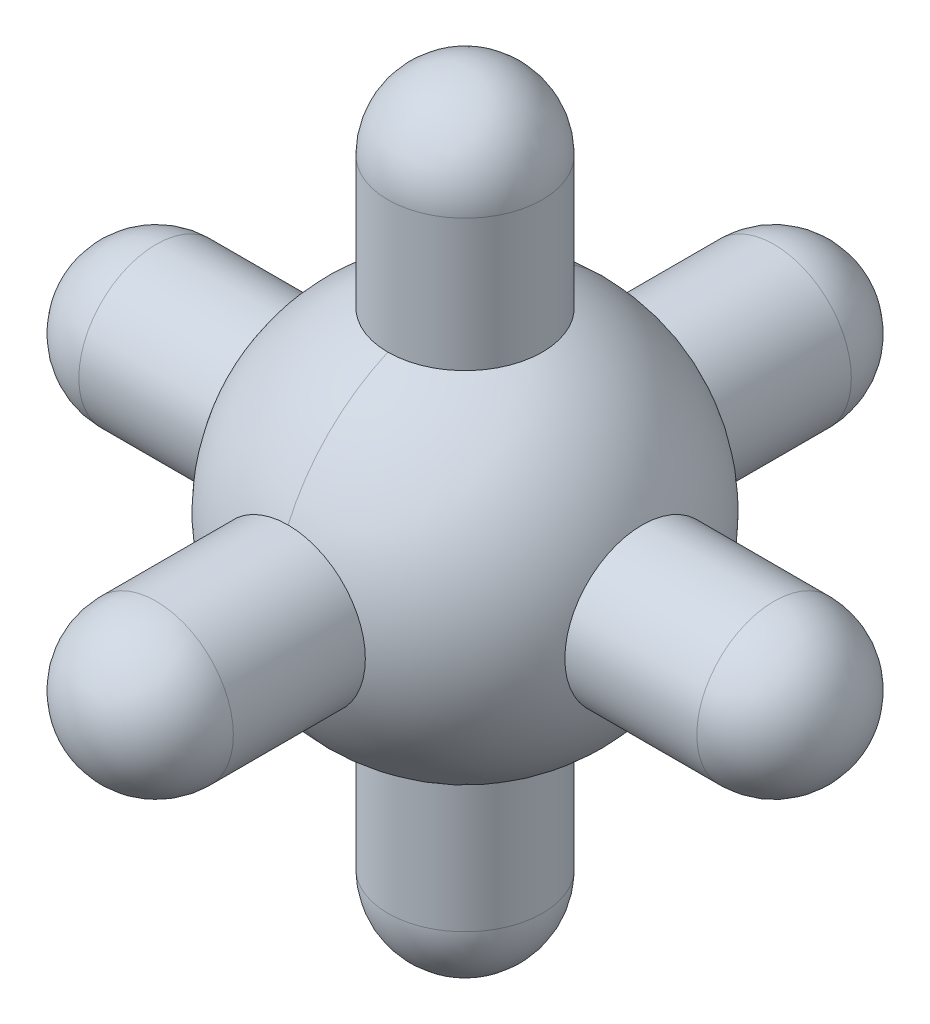
SolidWorks part; units mm, degrees
ref_plane "Front Plane" through (0, 0, 0) normal (0, 0, 1) x (1, 0, 0)
ref_plane "Top Plane" through (0, 0, 0) normal (0, 1, 0) x (1, 0, 0)
ref_plane "Right Plane" through (0, 0, 0) normal (1, 0, 0) x (0, 0, -1)
sketch "Sketch1" plane through (0, 0, 0) normal (1, 0, 0) x (0, 0, -1)
  circle A0 centre (0, 0) radius 25
  dimension "D1" = 50
extrude "Boss-Extrude1" add sketch "Sketch1" along normal mid plane 50
fillet "Fillet1" radius 25 2 edges at (-25, 0, -25) (25, 0, -25)
sketch "Sketch2" plane through (0, 0, 0) normal (1, 0, 0) x (0, 0, -1)
  circle A0 centre (0, 0) radius 10
  dimension "D1" = 20
extrude "Boss-Extrude2" add sketch "Sketch2" along normal mid plane 100
fillet "Fillet2" radius 10 2 edges at (-50, 0, -10) (50, 0, -10)
sketch "Sketch3" plane through (0, 0, 0) normal (0, 0, 1) x (1, 0, 0)
  circle A0 centre (0, 0) radius 10
  dimension "D1" = 20
extrude "Boss-Extrude3" add sketch "Sketch3" along normal mid plane 100
fillet "Fillet3" radius 10 2 edges at (10, 0, -50) (10, 0, 50)
sketch "Sketch4" plane through (0, 0, 0) normal (0, 1, 0) x (1, 0, 0)
  circle A0 centre (0, 0) radius 10
  dimension "D1" = 20
extrude "Boss-Extrude4" add sketch "Sketch4" along normal mid plane 100
fillet "Fillet4" radius 10 2 edges at (0, -50, 10) (0, 50, 10)
